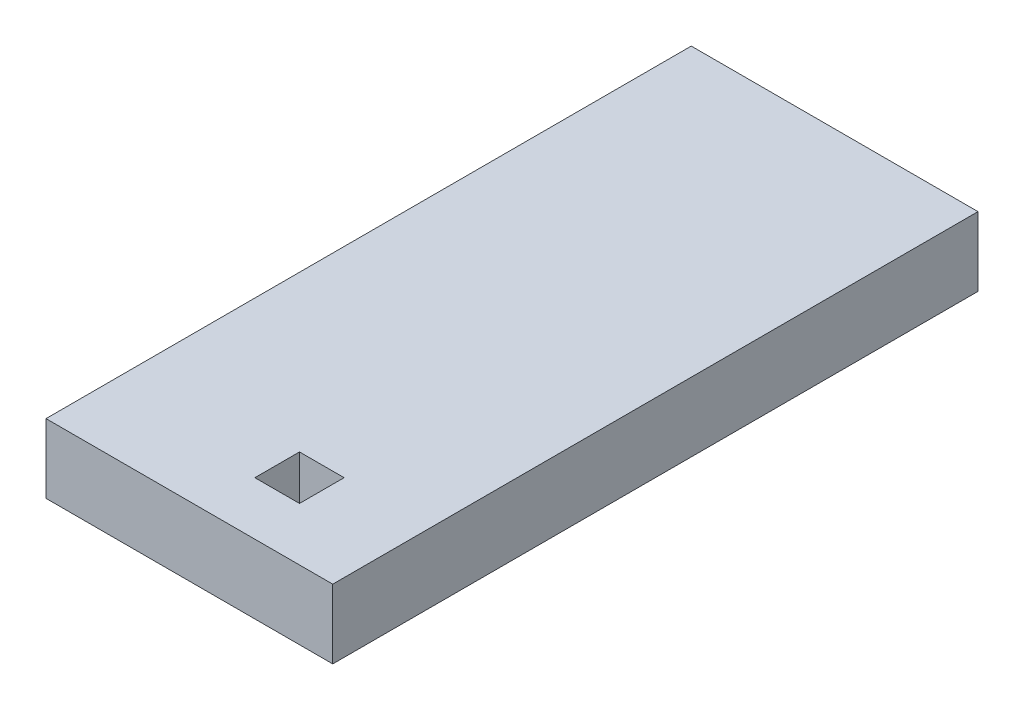
SolidWorks part; units mm, degrees
material "Acrylic (Medium-high impact)"
ref_plane "Front Plane" through (0, 0, 0) normal (0, 0, 1) x (1, 0, 0)
ref_plane "Top Plane" through (0, 0, 0) normal (0, 1, 0) x (1, 0, 0)
ref_plane "Right Plane" through (0, 0, 0) normal (1, 0, 0) x (0, 0, -1)
sketch "Sketch1" plane through (0, 0, 0) normal (0, 1, 0) x (1, 0, 0)
  line L0 (0, -11.3514) -> (0, 0) construction
  line L1 (5, -14.8236) -> (-5, -14.8236)
  line L2 (5, -14.8236) -> (5, 14.8236)
  line L3 (5, 14.8236) -> (-5, 14.8236)
  line L4 (-5, -14.8236) -> (-5, 14.8236)
  line L5 (5, -14.8236) -> (-5, 14.8236) construction
  line L6 (5, 14.8236) -> (-5, -14.8236) construction
  line L7 (-1.025, -10.3264) -> (1.025, -10.3264)
  line L8 (-1.025, -10.3264) -> (-1.025, -12.3764)
  line L9 (-1.025, -12.3764) -> (1.025, -12.3764)
  line L10 (1.025, -10.3264) -> (1.025, -12.3764)
  line L11 (-1.025, -10.3264) -> (1.025, -12.3764) construction
  line L12 (-1.025, -12.3764) -> (1.025, -10.3264) construction
  point P0 (0, 0)
  point P6 (0, -11.3514)
  dimension "D1" = 10
  dimension "D2" = 29.6472
  dimension "D3" = 2.05
  dimension "D4" = 26.175
extrude "Boss-Extrude1" add sketch "Sketch1" along normal blind 3.175 contours L1 L2 L3 L4 L7 L10 L9 L8 | L4 region at (0, 0, -0.1632)
sketch "Sketch2" plane through (0, 3.175, 0) normal (0, 1, 0) x (1, 0, 0)
  line L5 (5, -14.8236) -> (-5, -14.8236) construction
  line L6 (-5, 14.8236) -> (-8.175, 14.8236)
  line L7 (-5, 14.8236) -> (-5, -14.8236)
  line L8 (-5, -14.8236) -> (-8.175, -14.8236)
  line L9 (-8.175, 14.8236) -> (-8.175, -14.8236)
  dimension "D1" = 3.175
extrude "Boss-Extrude2" add sketch "Sketch2" against normal up to surface (3.175 mm away) up to face at (0, 0, 0)
equation "\"bottomThickness\"= .220in"
equation "\"wallThickness\"= .125in"
equation "\"D1@Boss-Extrude1\"=\"wallThickness\""
equation "\"D1@Sketch2\"=\"wallThickness\""
